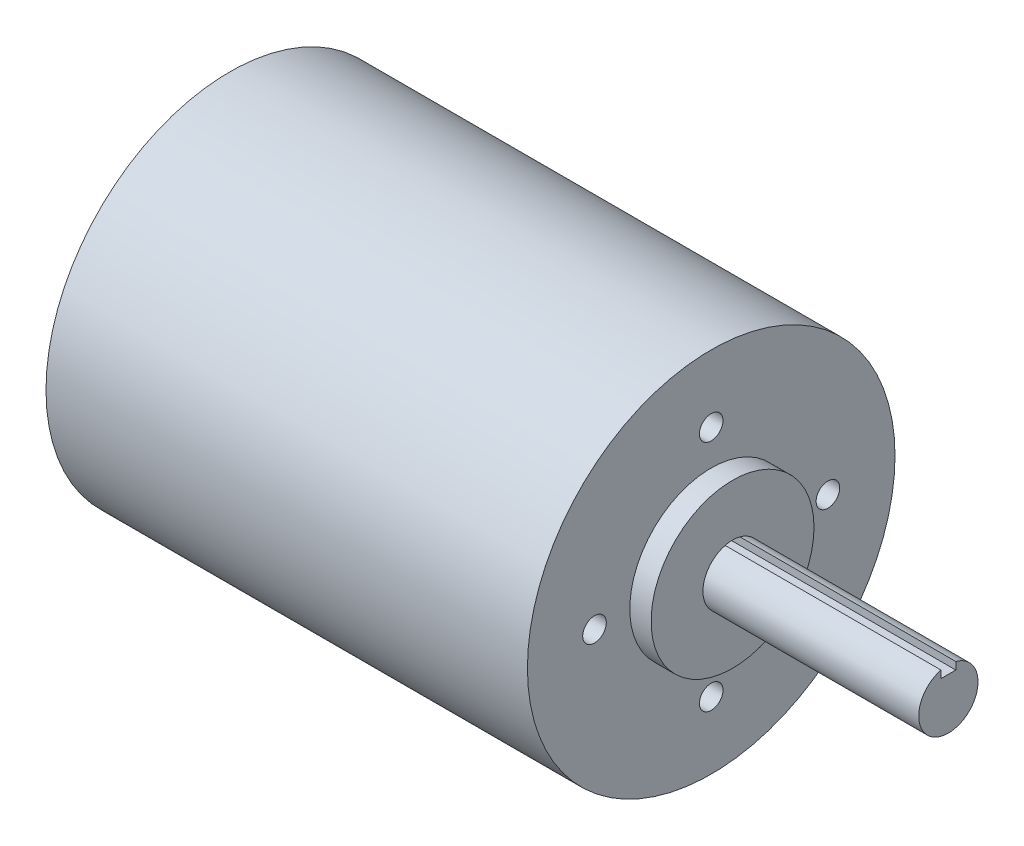
SolidWorks part; units mm, degrees
ref_plane "Front Plane" through (0, 0, 0) normal (0, 0, 1) x (1, 0, 0)
ref_plane "Top Plane" through (0, 0, 0) normal (0, 1, 0) x (1, 0, 0)
ref_plane "Right Plane" through (0, 0, 0) normal (1, 0, 0) x (0, 0, -1)
sketch "Sketch1" plane through (0, 0, 0) normal (1, 0, 0) x (0, 0, -1)
  circle A0 centre (0, 0) radius 39.37
  dimension "D1" = 78.74
extrude "Boss-Extrude1" add sketch "Sketch1" along normal blind 103.124
sketch "Sketch2" plane through (103.124, 0, 0) normal (1, 0, 0) x (0, 0, -1)
  line L0 (-1.5875, 6.1484) -> (-1.5875, 4.5609)
  line L1 (-1.5875, 4.5609) -> (1.5875, 4.5609)
  line L2 (0, 4.5609) -> (0, 0) construction
  line L3 (1.5875, 6.1484) -> (1.5875, 4.5609)
  arc A0 (-1.5875, 6.1484) -> (1.5875, 6.1484) centre (0, 0) ccw
  dimension "D1" = 12.7
  dimension "D2" = 3.175
  dimension "D3" = 1.5875
extrude "Boss-Extrude2" add sketch "Sketch2" along normal blind 50.8
hole_wizard "#8 (0.199) Diameter Hole1" positions "Sketch5" profile "Sketch4" hole size "#8" standard "Ansi Inch"
sketch "Sketch5" plane through (103.124, 0, 0) normal (1, 0, 0) x (0, 0, -1)
  point P0 (0, 25)
  dimension "D1" = 25
sketch "Sketch4" plane through (103.124, 25, 0) normal (0, 1, 0) x (0, 0, -1)
  line L0 (0, 0) -> (0, 11.5186)
  line L1 (0, 11.5186) -> (2.5273, 10)
  line L2 (2.5273, 10) -> (2.5273, 0)
  line L5 (2.5273, 0) -> (0, 0)
  line L10 (0, 11.5186) -> (-2.5273, 10) construction
  line L11 (0, -6.35) -> (0, 107.95) construction
  dimension "Hole Dia." = 5.0546
  dimension "Hole Depth" = 10
  dimension "Drill Angle" = 118
pattern_circular "CirPattern1" count 4 every 90 about axis through (153.924, 0, 0) along (-1, 0, 0) of "#8 (0.199) Diameter Hole1"
sketch "Sketch6" plane through (103.124, 0, 0) normal (1, 0, 0) x (0, 0, -1)
  circle A0 centre (0, 0) radius 6.35
  circle A1 centre (0, 0) radius 17.4498
  dimension "D1" = 12.7
  dimension "D2" = 34.8996
extrude "Boss-Extrude3" add sketch "Sketch6" along normal blind 4.572
sketch "Sketch7" plane through (0, 0, 0) normal (-1, 0, 0) x (0, 0, 1)
  circle A0 centre (0, 0) radius 4.7625
  dimension "D1" = 9.525
extrude "Boss-Extrude4" add sketch "Sketch7" along normal blind 12.7
hole_wizard "#4-40 Tapped Hole1" positions "Sketch9" profile "Sketch10" tap size "#4-40" standard "Ansi Inch"
sketch "Sketch9" plane through (0, 0, 0) normal (-1, 0, 0) x (0, 0, 1)
  line L0 (-23, 0) -> (23, 0) construction
  circle A0 centre (0, 0) radius 23 construction
  point P0 (-23, 0)
  point P1 (23, 0)
  dimension "D1" = 46
sketch "Sketch10" plane through (0, 0, -23) normal (0, 1, 0) x (0, 0, 1)
  line L0 (0, 0) -> (0, 8.2692)
  line L1 (0, 8.2692) -> (1.1303, 7.59)
  line L2 (1.1303, 7.59) -> (1.1303, 0)
  line L5 (1.1303, 0) -> (0, 0)
  line L10 (0, 8.2692) -> (-1.1303, 7.59) construction
  line L11 (0, -6.35) -> (0, 107.95) construction
  dimension "Tap Drill Dia." = 2.2606
  dimension "Tap Drill Depth" = 7.59
  dimension "Drill Angle" = 118
hole_wizard "#6-32 Tapped Hole1" positions "Sketch12" profile "Sketch11" tap size "#6-32" standard "Ansi Inch"
sketch "Sketch12" plane through (0, 0, 0) normal (-1, 0, 0) x (0, 0, 1)
  line L0 (-19.8136, 28.2968) -> (19.8136, -28.2968)
  line L2 (-28.2968, -19.8136) -> (28.2968, 19.8136)
  line L4 (0, 0) -> (34.544, 0) construction
  circle A0 centre (0, 0) radius 34.544
  point P0 (28.2968, 19.8136)
  point P1 (-28.2968, -19.8136)
  point P3 (19.8136, -28.2968)
  point P5 (-19.8136, 28.2968)
  dimension "D1" = 69.088
  dimension "D2" = 35
sketch "Sketch11" plane through (0, 19.8136, 28.2968) normal (0, 1, 0) x (0, 0, 1)
  line L0 (0, 0) -> (0, 10.2027)
  line L1 (0, 10.2027) -> (1.3525, 9.39)
  line L2 (1.3525, 9.39) -> (1.3525, 0)
  line L5 (1.3525, 0) -> (0, 0)
  line L10 (0, 10.2027) -> (-1.3526, 9.39) construction
  line L11 (0, -6.35) -> (0, 107.95) construction
  dimension "Tap Drill Dia." = 2.7051
  dimension "Tap Drill Depth" = 9.39
  dimension "Drill Angle" = 118
